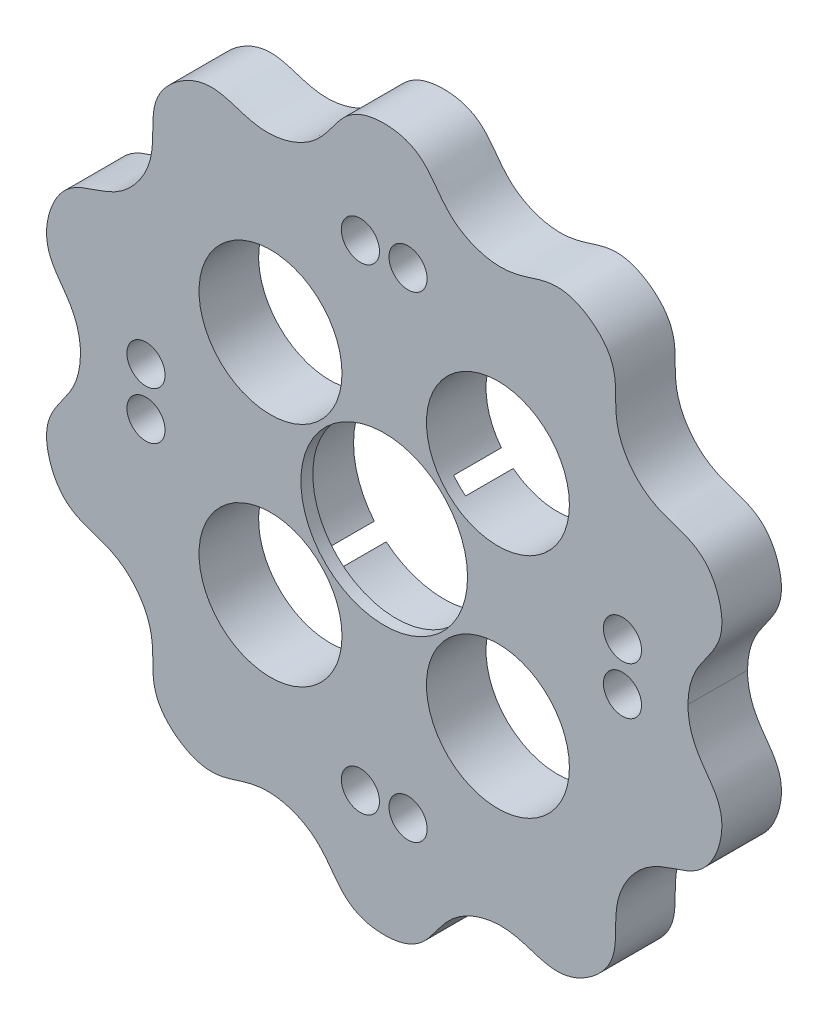
SolidWorks part; units mm, degrees
ref_plane "Front Plane" through (0, 0, 0) normal (0, 0, 1) x (1, 0, 0)
ref_plane "Top Plane" through (0, 0, 0) normal (0, 1, 0) x (1, 0, 0)
ref_plane "Right Plane" through (0, 0, 0) normal (1, 0, 0) x (0, 0, -1)
ref_plane "Plane1" through (0, 0, 4) normal (0, 0, 1) x (1, 0, 0)
sketch "Sketch3" plane through (0, 0, 4) normal (0, 0, 1) x (1, 0, 0)
  circle A0 centre (2, 0) radius 7.5
  spline S0 degree 5 poles (-23.5, 0) (-23.5, -0.6619) (-23.5985, -1.4561) (-23.8874, -2.4734) (-24.5265, -3.4803) (-25.3239, -4.5428) (-25.7599, -5.1922) (-26.203, -6.107) (-26.3992, -6.9747) (-26.3685, -8.1757) (-26.0322, -9.4106) (-25.4671, -10.5179) (-24.8895, -11.2256) (-23.9802, -11.9083) (-23.1576, -12.2723) (-21.7572, -12.687) (-20.1242, -13.2676) (-18.7699, -14.5833) (-17.7259, -16.1905) (-17.3933, -18.0022) (-17.4393, -19.3418) (-17.4288, -20.3924) (-17.2271, -21.518) (-16.8759, -22.3353) (-16.145, -23.2889) (-15.1471, -24.0902) (-14.0391, -24.6539) (-13.1558, -24.8869) (-12.0189, -24.9048) (-11.1394, -24.7158) (-9.7628, -24.2281) (-8.1004, -23.738) (-6.2314, -24.0063) (-4.442, -24.693) (-3.1081, -25.9632) (-2.3579, -27.074) (-1.7319, -27.9177) (-0.9071, -28.7098) (-0.1425, -29.1646) (1.0093, -29.5065) (2.2876, -29.5682) (3.5153, -29.373) (4.3668, -29.0423) (5.2971, -28.3885) (5.8976, -27.7187) (6.7246, -26.515) (7.7814, -25.1413) (9.4513, -24.2598) (11.3025, -23.7636) (13.1282, -24.0071) (14.3881, -24.4648) (15.3905, -24.7795) (16.5233, -24.9355) (17.4092, -24.854) (18.5419, -24.4536) (19.6124, -23.7522) (20.4909, -22.8726) (20.9855, -22.1045) (21.3538, -21.0288) (21.4458, -20.1339) (21.4074, -18.674) (21.455, -16.9415) (22.2878, -15.2469) (23.4937, -13.7573) (25.1139, -12.8812) (26.4022, -12.5109) (27.3981, -12.1763) (28.4063, -11.6367) (29.0751, -11.05) (29.7562, -10.0602) (30.2099, -8.8636) (30.4037, -7.6356) (30.3523, -6.7236) (30.018, -5.6368) (29.5664, -4.8587) (28.6772, -3.7002) (27.9235, -2.6005) (27.5985, -1.4561) (27.5, -0.6619) (27.5, 0) knots 0.5 0.5 0.5 0.5 0.5 0.5 0.516667 0.52 0.526667 0.53 0.533333 0.536667 0.546667 0.55 0.56 0.563333 0.566667 0.57 0.58 0.583333 0.6 0.61 0.616667 0.626667 0.63 0.633333 0.636667 0.646667 0.65 0.66 0.663333 0.666667 0.67 0.68 0.683333 0.7 0.71 0.716667 0.726667 0.73 0.733333 0.736667 0.746667 0.75 0.76 0.763333 0.766667 0.77 0.78 0.783333 0.8 0.81 0.816667 0.826667 0.83 0.833333 0.836667 0.846667 0.85 0.86 0.863333 0.866667 0.87 0.88 0.883333 0.9 0.91 0.916667 0.926667 0.93 0.933333 0.936667 0.946667 0.95 0.96 0.963333 0.966667 0.97 0.98 0.983333 1 1 1 1 1 1 weights 1 1 1 1 1 1 1 1 1 1 1 1 1 1 1 1 1 1 1 1 1 1 1 1 1 1 1 1 1 1 1 1 1 1 1 1 1 1 1 1 1 1 1 1 1 1 1 1 1 1 1 1 1 1 1 1 1 1 1 1 1 1 1 1 1 1 1 1 1 1 1 1 1 1 1 1 1 1 1 1
  spline S1 degree 5 poles (27.5, 0) (27.5, 0.6619) (27.5985, 1.4561) (27.8874, 2.4734) (28.5265, 3.4803) (29.3239, 4.5428) (29.7599, 5.1922) (30.203, 6.107) (30.3992, 6.9747) (30.3685, 8.1757) (30.0322, 9.4106) (29.4671, 10.5179) (28.8895, 11.2256) (27.9802, 11.9083) (27.1576, 12.2723) (25.7572, 12.687) (24.1242, 13.2676) (22.7699, 14.5833) (21.7259, 16.1905) (21.3933, 18.0022) (21.4393, 19.3418) (21.4288, 20.3924) (21.2271, 21.518) (20.8759, 22.3353) (20.145, 23.2889) (19.1471, 24.0902) (18.0391, 24.6539) (17.1558, 24.8869) (16.0189, 24.9048) (15.1394, 24.7158) (13.7628, 24.2281) (12.1004, 23.738) (10.2314, 24.0063) (8.442, 24.693) (7.1081, 25.9632) (6.3579, 27.074) (5.7319, 27.9177) (4.9071, 28.7098) (4.1425, 29.1646) (2.9907, 29.5065) (1.7124, 29.5682) (0.4847, 29.373) (-0.3668, 29.0423) (-1.2971, 28.3885) (-1.8976, 27.7187) (-2.7246, 26.515) (-3.7814, 25.1413) (-5.4513, 24.2598) (-7.3025, 23.7636) (-9.1282, 24.0071) (-10.3881, 24.4648) (-11.3905, 24.7795) (-12.5233, 24.9355) (-13.4092, 24.854) (-14.5419, 24.4536) (-15.6124, 23.7522) (-16.4909, 22.8726) (-16.9855, 22.1045) (-17.3538, 21.0288) (-17.4458, 20.1339) (-17.4074, 18.674) (-17.455, 16.9415) (-18.2878, 15.2469) (-19.4937, 13.7573) (-21.1139, 12.8812) (-22.4022, 12.5109) (-23.3981, 12.1763) (-24.4063, 11.6367) (-25.0751, 11.05) (-25.7562, 10.0602) (-26.2099, 8.8636) (-26.4037, 7.6356) (-26.3523, 6.7236) (-26.018, 5.6368) (-25.5664, 4.8587) (-24.6772, 3.7002) (-23.9235, 2.6005) (-23.5985, 1.4561) (-23.5, 0.6619) (-23.5, 0) knots 0 0 0 0 0 0 0.016667 0.02 0.026667 0.03 0.033333 0.036667 0.046667 0.05 0.06 0.063333 0.066667 0.07 0.08 0.083333 0.1 0.11 0.116667 0.126667 0.13 0.133333 0.136667 0.146667 0.15 0.16 0.163333 0.166667 0.17 0.18 0.183333 0.2 0.21 0.216667 0.226667 0.23 0.233333 0.236667 0.246667 0.25 0.26 0.263333 0.266667 0.27 0.28 0.283333 0.3 0.31 0.316667 0.326667 0.33 0.333333 0.336667 0.346667 0.35 0.36 0.363333 0.366667 0.37 0.38 0.383333 0.4 0.41 0.416667 0.426667 0.43 0.433333 0.436667 0.446667 0.45 0.46 0.463333 0.466667 0.47 0.48 0.483333 0.5 0.5 0.5 0.5 0.5 0.5 weights 1 1 1 1 1 1 1 1 1 1 1 1 1 1 1 1 1 1 1 1 1 1 1 1 1 1 1 1 1 1 1 1 1 1 1 1 1 1 1 1 1 1 1 1 1 1 1 1 1 1 1 1 1 1 1 1 1 1 1 1 1 1 1 1 1 1 1 1 1 1 1 1 1 1 1 1 1 1 1 1
extrude "CYC Disk" add sketch "Sketch3" along normal blind 5
sketch "Sketch6" plane through (0, 0, 9) normal (0, 0, 1) x (1, 0, 0)
  line L0 (0, 0) -> (2, 0) construction
  circle A1 centre (2, 0) radius 7.575
  dimension "D2" = 15.15
  dimension "D1" = 2
extrude "Cam Bearing" cut sketch "Sketch6" against normal through all
sketch "Sketch8" plane through (0, 0, 9) normal (0, 0, 1) x (1, 0, 0)
  circle A0 centre (2, 0) radius 6.9953
  circle A1 centre (2, 0) radius 7.575
extrude "Cam Bearing Retainer" add sketch "Sketch8" against normal blind 1
sketch "Sketch9" plane through (0, 0, 9) normal (0, 0, 1) x (1, 0, 0)
  line L0 (2, 0) -> (2, 20) construction
  line L2 (4, 20) -> (2, 20)
  line L3 (2, 20) -> (0, 20)
  circle A2 centre (0, 20) radius 1.6
  circle A3 centre (4, 20) radius 1.6
  circle A4 centre (22, -2) radius 1.6
  circle A5 centre (22, 2) radius 1.6
  circle A6 centre (0, -20) radius 1.6
  circle A7 centre (4, -20) radius 1.6
  circle A8 centre (-18, 2) radius 1.6
  circle A9 centre (-18, -2) radius 1.6
  point P23 (2, 0)
  dimension "D3" = 2
  dimension "D4" = 3.2
  dimension "D5" = 3.2
  dimension "D6" = 4
  dimension "D1" = 2
  dimension "D2" = 20
extrude "Positioning Holes" cut sketch "Sketch9" against normal through all contours A3 | A5 | A4 | A7 | A6 | A9 | A8 | A2 region at (4, 21.5547, 9) region at (22, -2, 9) region at (22, 2, 9) region at (0, -20, 9) region at (4, -20, 9) region at (-18, 2, 9) region at (-18, -2, 9)
sketch "CYC Ouput Sketch" plane through (2, 0, 4) normal (0, 0, 1) x (1, 0, 0)
  line L1 (9.5459, 9.5459) -> (-9.5459, 9.5459) construction
  line L2 (-9.5459, 9.5459) -> (-9.5459, -9.5459) construction
  line L3 (-9.5459, -9.5459) -> (9.5459, -9.5459) construction
  line L4 (9.5459, -9.5459) -> (9.5459, 9.5459) construction
  circle A0 centre (0, 0) radius 13.5 construction
sketch "Sketch11" plane through (0, 0, 9) normal (0, 0, 1) x (1, 0, 0)
  circle A0 centre (11.5459, 9.5459) radius 6
  circle A1 centre (11.5459, -9.5459) radius 6
  circle A2 centre (-7.5459, -9.5459) radius 6
  circle A3 centre (-7.5459, 9.5459) radius 6
  dimension "D1" = 12
extrude "Output Holes" cut sketch "Sketch11" against normal through all
equation "\"CamBearingOut\"=15.15"
equation "\"D2@Sketch6\"=\"CamBearingOut\""
equation "\"RingPinShaft\"= 5"
equation "\"CenterBearingOut\"=32"
equation "\"RingPostIn\"=5"
